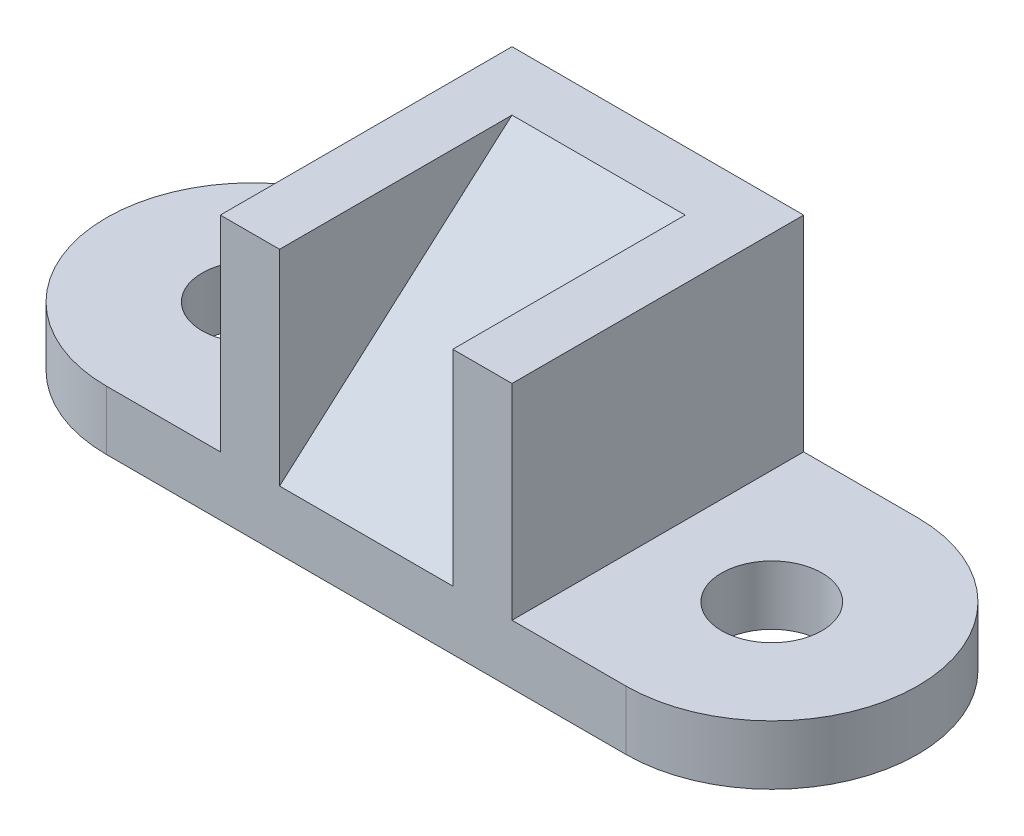
SolidWorks part; units mm, degrees
ref_plane "Front Plane" through (0, 0, 0) normal (0, 0, 1) x (1, 0, 0)
ref_plane "Top Plane" through (0, 0, 0) normal (0, 1, 0) x (1, 0, 0)
ref_plane "Right Plane" through (0, 0, 0) normal (1, 0, 0) x (0, 0, -1)
sketch "Sketch1" plane through (0, 0, 0) normal (0, 1, 0) x (1, 0, 0)
  line L0 (0, 0) -> (-57, 0)
  line L1 (-57, 0) -> (-57, 64)
  line L2 (-57, 64) -> (0, 64)
  line L3 (0, 64) -> (0, 0)
  circle A0 centre (-57, 32) radius 32
  dimension "D1" = 57
  dimension "D2" = 64
extrude "Boss-Extrude1" add sketch "Sketch1" along normal blind 13 contours L1 A0 | A0 L0 L3 L2 | L1 A0 region at (-16.734, 0, -32) region at (-70.5812, 0, -32) region at (-43.4188, 0, -32)
sketch "Sketch2" plane through (0, 13, 0) normal (0, 1, 0) x (1, 0, 0)
  circle A0 centre (-57, 32) radius 11
  dimension "D1" = 22
extrude "Cut-Extrude1" cut sketch "Sketch2" against normal through all
sketch "Sketch3" plane through (0, 13, 0) normal (0, 1, 0) x (1, 0, 0)
  line L0 (0, 0) -> (-32, 0)
  line L1 (0, 0) -> (-57, 0) construction
  line L2 (-32, 0) -> (-32, 64)
  line L3 (-57, 64) -> (0, 64) construction
  line L4 (-32, 64) -> (0, 64)
  line L5 (0, 64) -> (0, 0)
  dimension "D1" = 32
extrude "Boss-Extrude2" add sketch "Sketch3" along normal blind 45
sketch "Sketch4" plane through (0, 0, 0) normal (1, 0, 0) x (0, 0, -1)
  line L0 (0, 13) -> (51, 58)
  line L1 (0, 58) -> (0, 0) construction
  line L2 (0, 58) -> (64, 58) construction
  line L3 (51, 58) -> (0, 58)
  line L4 (0, 58) -> (0, 13)
  dimension "D1" = 13
  dimension "D2" = 13
extrude "Cut-Extrude2" cut sketch "Sketch4" against normal blind 19
ref_plane "Plane1" through (0, 0, 0) normal (1, 0, 0) x (0, 0, -1)
mirror "Mirror1" about plane through (0, 0, 0) normal (1, 0, 0) of "Cut-Extrude1", "Cut-Extrude2", "Boss-Extrude1", "Boss-Extrude2"
